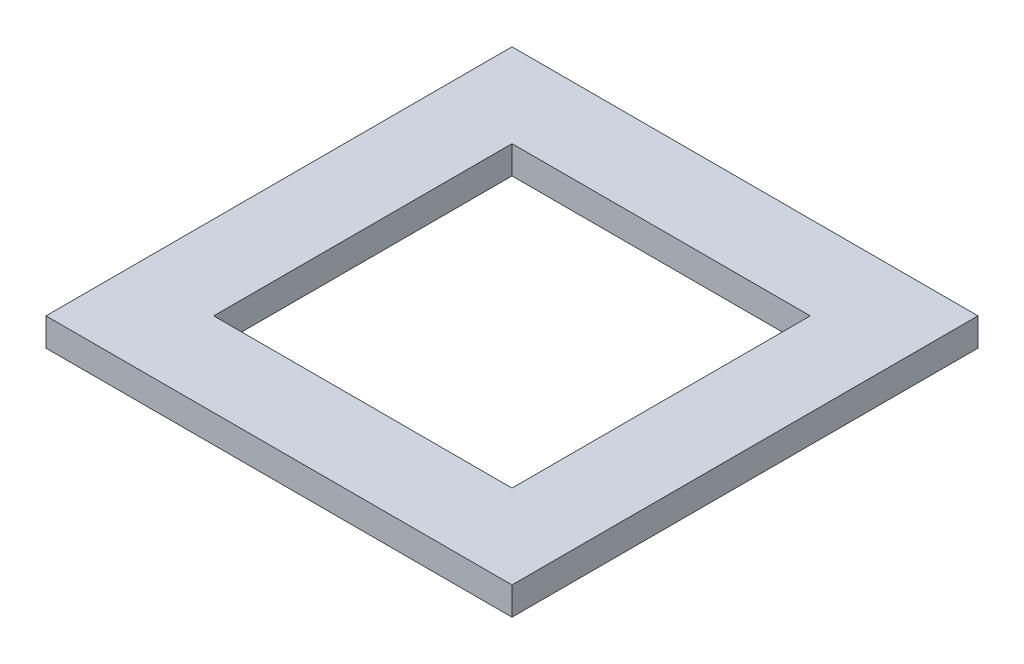
SolidWorks part; units mm, degrees
ref_plane "Front Plane" through (0, 0, 0) normal (0, 0, 1) x (1, 0, 0)
ref_plane "Top Plane" through (0, 0, 0) normal (0, 1, 0) x (1, 0, 0)
ref_plane "Right Plane" through (0, 0, 0) normal (1, 0, 0) x (0, 0, -1)
sketch "Sketch1" plane through (0, 0, 0) normal (0, 1, 0) x (1, 0, 0)
  line L1 (-25, 25) -> (25, 25)
  line L2 (-25, 25) -> (-25, -25)
  line L3 (-25, -25) -> (25, -25)
  line L4 (25, 25) -> (25, -25)
  line L5 (-16, -16) -> (16, -16)
  line L6 (-16, -16) -> (-16, 16)
  line L7 (-16, 16) -> (16, 16)
  line L8 (16, -16) -> (16, 16)
  point P4 (0, 25)
  point P6 (-25, 0)
  point P11 (16, 0)
  point P12 (0, 16)
  dimension "D1" = 50
  dimension "D2" = 32
  dimension "D3" = 32
extrude "Boss-Extrude1" add sketch "Sketch1" along normal blind 3
sketch "Sketch3" plane through (0, 0, 0) normal (0, 1, 0) x (1, 0, 0)
  line L0 (-22, 22) -> (-22, -22) construction
  line L1 (-22, -22) -> (22, -22) construction
  circle A0 centre (-22, 22) radius 1.8
  circle A1 centre (22, 22) radius 1.8
  circle A2 centre (22, -22) radius 1.8
  circle A3 centre (-22, -22) radius 1.8
  point P8 (0, -22)
  point P9 (-22, 0)
  dimension "D1" = 3.6
  dimension "D2" = 44
  dimension "D3" = 44
extrude "Cut-Extrude1" cut sketch "Sketch3" along normal blind 1.5
